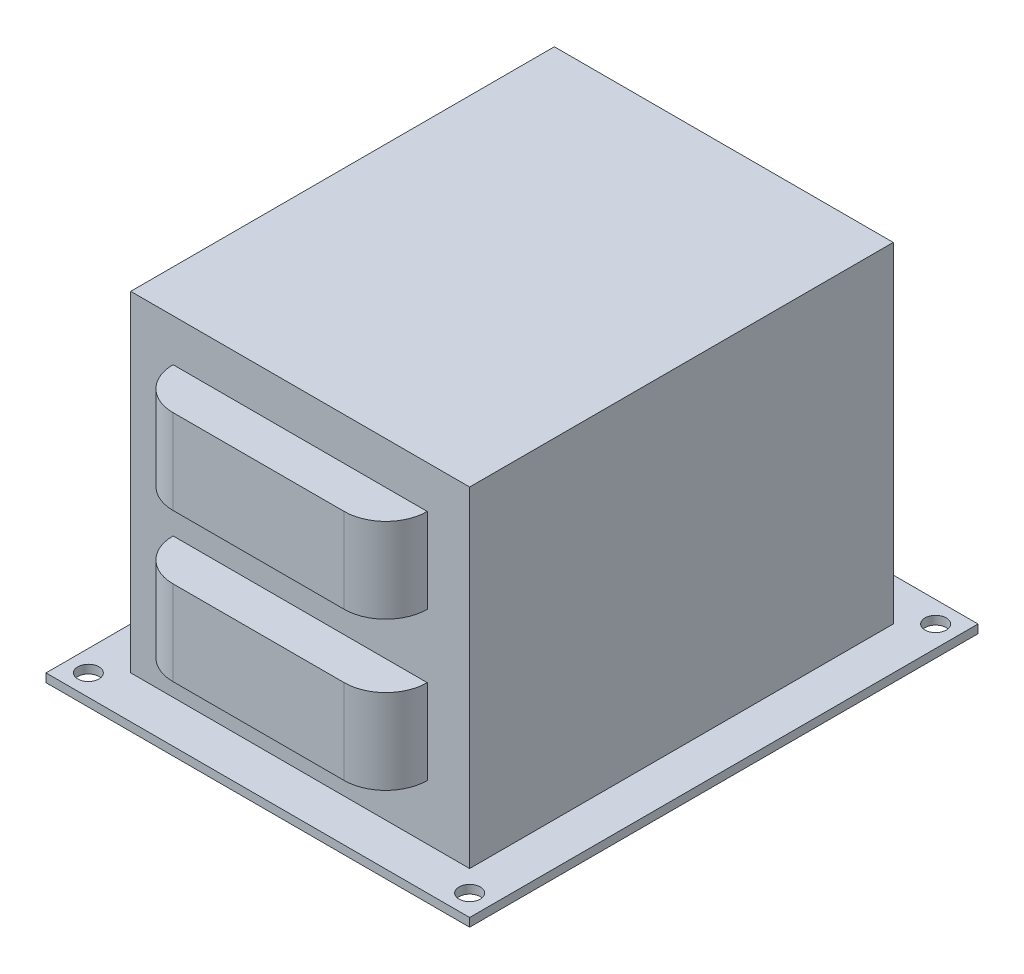
SolidWorks part; units mm, degrees
ref_plane "Front Plane" through (0, 0, 0) normal (0, 0, 1) x (1, 0, 0)
ref_plane "Top Plane" through (0, 0, 0) normal (0, 1, 0) x (1, 0, 0)
ref_plane "Right Plane" through (0, 0, 0) normal (1, 0, 0) x (0, 0, -1)
sketch "Sketch1" plane through (0, 0, 0) normal (0, 1, 0) x (1, 0, 0)
  line L0 (26.4288, 0) -> (0, 0) construction
  line L1 (-63.5, 76.2) -> (63.5, 76.2)
  line L2 (-63.5, 76.2) -> (-63.5, -76.2)
  line L3 (-63.5, -76.2) -> (63.5, -76.2)
  line L4 (63.5, 76.2) -> (63.5, -76.2)
  line L5 (-63.5, 76.2) -> (63.5, -76.2) construction
  line L6 (-63.5, -76.2) -> (63.5, 76.2) construction
  line L7 (-50.8, 63.5) -> (50.8, 63.5)
  line L8 (-50.8, 63.5) -> (-50.8, -63.5)
  line L9 (-50.8, -63.5) -> (50.8, -63.5)
  line L10 (50.8, 63.5) -> (50.8, -63.5)
  line L11 (-50.8, 63.5) -> (50.8, -63.5) construction
  line L12 (-50.8, -63.5) -> (50.8, 63.5) construction
  line L13 (0, 0) -> (0, 22.2605) construction
  line L14 (25.654, 75.946) -> (-25.654, 75.946)
  line L15 (-38.1, 63.5) -> (38.1, 63.5)
  line L16 (-38.1, -63.5) -> (38.1, -63.5)
  line L17 (25.654, -75.946) -> (-25.654, -75.946)
  arc A0 (-25.654, 75.946) -> (-38.1, 63.5) centre (-25.654, 63.5) ccw
  arc A1 (25.654, 75.946) -> (38.1, 63.5) centre (25.654, 63.5) cw
  arc A2 (25.654, -75.946) -> (38.1, -63.5) centre (25.654, -63.5) ccw
  arc A3 (-25.654, -75.946) -> (-38.1, -63.5) centre (-25.654, -63.5) cw
  circle A4 centre (-57.15, 69.85) radius 3.175
  circle A5 centre (57.15, 69.85) radius 3.175
  circle A6 centre (57.15, -69.85) radius 3.175
  circle A7 centre (-57.15, -69.85) radius 3.175
  point P0 (0, 0)
  point P6 (0, 0)
  dimension "D9" = 6.35
  dimension "D1" = 127
  dimension "D2" = 152.4
  dimension "D3" = 12.7
  dimension "D4" = 12.7
  dimension "D5" = 12.446
  dimension "D6" = 12.7
  dimension "D7" = 6.35
  dimension "D8" = 6.35
extrude "Boss-Extrude1" add sketch "Sketch1" along normal blind 2.54 contours L4 L1 L2 L3 A5 A4 L17 A3 L9 L8 L7 A0 L14 A1 L10 A2 A6 A7 | A3 L17 A2 L9 | L10 L7 L8 L9 | A1 L14 A0 L7 region at (0, 0, -76.0016) region at (0, 0, 0) region at (0, 0, -69.4634) region at (0, 0, 69.4634)
extrude "Boss-Extrude2" add sketch "Sketch1<4>" along normal blind 101.6 contours L10 L7 L8 L9 region at (0, 0, 0)
sketch "Sketch1<4>" plane through (0, 0, 0) normal (0, 1, 0) x (1, 0, 0) same geometry as "Sketch1"
extrude "Boss-Extrude3" add sketch "Sketch1<5>" along normal offset from surface (25.4 mm away) 12.7 from offset 63.5 contours A3 L17 A2 L9 | L14 A0 L15 A1 region at (0, 0, 69.4634) up to face at (0, 101.6, 0)
sketch "Sketch1<5>" plane through (0, 0, 0) normal (0, 1, 0) x (1, 0, 0) same geometry as "Sketch1"
extrude "Boss-Extrude4" add sketch "Sketch1<6>" along normal blind 25.4 from offset 19.05 contours A3 L17 A2 L9 | A1 L14 A0 L7 region at (0, 0, -69.4634) region at (0, 0, 69.4634)
sketch "Sketch1<6>" plane through (0, 0, 0) normal (0, 1, 0) x (1, 0, 0) same geometry as "Sketch1"
